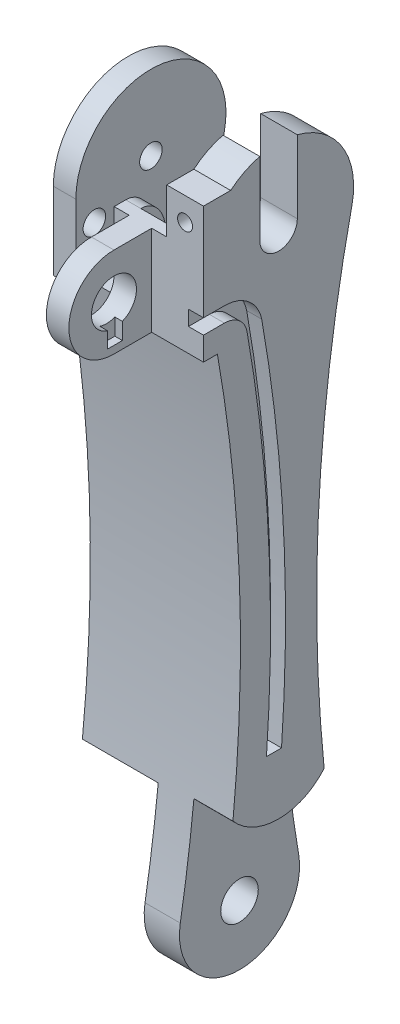
SolidWorks part; units mm, degrees
ref_plane "Front Plane" through (0, 0, 0) normal (0, 0, 1) x (1, 0, 0)
ref_plane "Top Plane" through (0, 0, 0) normal (0, 1, 0) x (1, 0, 0)
ref_plane "Right Plane" through (0, 0, 0) normal (1, 0, 0) x (0, 0, -1)
sketch "Sketch1" plane through (0, 0, 0) normal (1, 0, 0) x (0, 0, -1)
  arc A0 (9.7654, 20.1165) -> (-9.7654, 20.1165) centre (0, 22.2701) ccw
  arc A1 (-7.8874, -56.3924) -> (7.8874, -56.3924) centre (0, -57.7299) ccw
  arc A2 (-7.8874, -56.3924) -> (-9.7654, 20.1165) centre (-205.0724, -22.9549) ccw
  circle A3 centre (0, 22.2701) radius 1.5
  arc A4 (9.7654, 20.1165) -> (7.8874, -56.3924) centre (205.0724, -22.9549) ccw
  circle A5 centre (0, -57.7299) radius 2.5
extrude "Boss-Extrude1" add sketch "Sketch1" along normal blind 20
sketch "Sketch2" plane through (0, 0, 0) normal (0, 0, 1) x (1, 0, 0)
  line L1 (0, -65.7299) -> (8.1, -65.7299)
  line L2 (0, -65.7299) -> (0, -45.7299)
  line L3 (0, -45.7299) -> (8.1, -45.7299)
  line L4 (8.1, -65.7299) -> (8.1, -45.7299)
  line L5 (20, -65.7299) -> (14.8, -65.7299)
  line L6 (20, -65.7299) -> (20, -45.7299)
  line L7 (20, -45.7299) -> (14.8, -45.7299)
  line L8 (14.8, -65.7299) -> (14.8, -45.7299)
  line L11 (3, 32.2701) -> (8.1, 32.2701)
  line L12 (3, 32.2701) -> (3, 12.2701)
  line L13 (3, 12.2701) -> (8.1, 12.2701)
  line L14 (8.1, 32.2701) -> (8.1, 12.2701)
extrude "Cut-Extrude1" cut sketch "Sketch2" against normal blind 20 and the other way blind 20
sketch "Sketch3" plane through (8.1, 0, 0) normal (-1, 0, 0) x (0, 0, 1)
  line L0 (8.5, 22.2701) -> (8.5, 40.9095)
  line L1 (8.5, 40.9095) -> (-17.5287, 40.9095)
  line L2 (-17.5287, 40.9095) -> (-17.5287, 13.7701)
  line L3 (0, 13.7701) -> (-17.5287, 13.7701)
  arc A0 (0, 13.7701) -> (8.5, 22.2701) centre (0, 22.2701) ccw
extrude "Cut-Extrude2" cut sketch "Sketch3" against normal blind 9
sketch "Sketch4" plane through (8.1, 0, 0) normal (-1, 0, 0) x (0, 0, 1)
  line L0 (8.5, 27.5379) -> (8.2838, 12.7416)
  line L1 (8.2838, 12.7416) -> (10.2838, 12.7416)
  line L2 (10.2838, 12.7416) -> (10.2838, 27.5379)
  line L3 (10.2838, 27.5379) -> (8.5, 27.5379)
  arc A0 (9.7654, 20.1165) -> (6.3734, -45.7299) centre (205.0724, -22.9549) ccw construction
extrude "Boss-Extrude2" add sketch "Sketch4" against normal through all
sketch "Sketch5" plane through (8.1, 0, 0) normal (-1, 0, 0) x (0, 0, 1)
  line L4 (8.1452, 11.9686) -> (8.4478, 23.9686)
  line L6 (15.0224, 23.9686) -> (9.8547, 23.9686)
  line L8 (8.1452, 11.9686) -> (15.0224, 11.9686)
  line L9 (8.5, 27.5379) -> (8.4045, 20.9993) construction
  line L10 (8.4478, 23.9686) -> (9.8547, 23.9686)
  circle A2 centre (15.0224, 17.9686) radius 3
  arc A5 (15.0224, 11.9686) -> (15.0224, 23.9686) centre (15.0224, 17.9686) ccw
  arc A6 (9.7654, 20.1165) -> (-9.7654, 20.1165) centre (0, 22.2701) ccw construction
  arc A7 (9.7654, 20.1165) -> (6.3734, -45.7299) centre (205.0724, -22.9549) ccw construction
extrude "Boss-Extrude3" add sketch "Sketch5" against normal blind 5
sketch "Sketch12" plane through (13.1, 0, 0) normal (1, 0, 0) x (0, 0, -1)
  line L2 (-13.9029, 14.9686) -> (-13.9029, 12.9686)
  line L4 (-15.9029, 14.9686) -> (-15.9029, 15.2943)
  line L5 (-15.9029, 15.2943) -> (-13.9029, 15.2943)
  line L6 (-13.9029, 12.9686) -> (-15.9029, 12.9686)
  line L7 (-13.9029, 14.9686) -> (-13.9029, 15.2943)
  line L11 (-15.9029, 14.9686) -> (-15.9029, 12.9686)
extrude "Cut-Extrude6" cut sketch "Sketch12" against normal blind 1
sketch "Sketch13" plane through (17.1, 0, 0) normal (-1, 0, 0) x (0, 0, 1)
  circle A0 centre (0, 22.2701) radius 2.5
extrude "Cut-Extrude7" cut sketch "Sketch13" against normal blind 4
sketch "Sketch15" plane through (0, 0, 0) normal (-1, 0, 0) x (0, 0, 1)
  line L0 (10, 22.2701) -> (10, 11.9686)
  line L1 (8.1452, 11.9686) -> (15.0224, 11.9686) construction
  line L2 (10, 11.9686) -> (8.1452, 11.9686)
  line L3 (10, 22.2701) -> (7.5957, 11.9686)
  line L4 (7.5957, 11.9686) -> (8.1452, 11.9686)
  arc A0 (9.7654, 20.1165) -> (-9.7654, 20.1165) centre (0, 22.2701) ccw construction
extrude "Boss-Extrude4" add sketch "Sketch15" against normal blind 3
sketch "Sketch16" plane through (20, 0, 0) normal (1, 0, 0) x (0, 0, -1)
  line L0 (-10.2838, 23.9686) -> (-9.8547, 23.9686)
  line L1 (-10.2838, 23.9686) -> (-10.2838, 27.5379)
  line L2 (-10.2838, 27.5379) -> (-8.5, 27.5379) construction
  line L3 (-10.2838, 12.7416) -> (-10.2838, 27.5379) construction
  line L4 (-10.2838, 27.5379) -> (-8.5, 27.5379)
  arc A0 (-8.5, 27.5379) -> (-9.8547, 23.9686) centre (0, 22.2701) ccw
extrude "Cut-Extrude9" cut sketch "Sketch16" against normal blind 3
sketch "Sketch17" plane through (0, 0, 10.2838) normal (0, 0, 1) x (1, 0, 0)
  line L1 (17.1, 27.5379) -> (8.1, 27.5379)
  line L2 (17.1, 27.5379) -> (17.1, 23.9686)
  line L3 (17.1, 23.9686) -> (8.1, 23.9686)
  line L4 (8.1, 27.5379) -> (8.1, 23.9686)
extrude "Cut-Extrude11" cut sketch "Sketch17" against normal blind 3
sketch "Sketch18" plane through (13.1, 0, 0) normal (1, 0, 0) x (0, 0, -1)
  line L1 (-10.2838, 12.7416) -> (-4.5128, 12.7416)
  line L2 (-10.2838, 12.7416) -> (-10.2838, 11.9686)
  line L3 (-10.2838, 11.9686) -> (-4.5128, 11.9686)
  line L4 (-4.5128, 12.7416) -> (-4.5128, 11.9686)
extrude "Boss-Extrude5" add sketch "Sketch18" along normal through all and the other way blind 1
sketch "Sketch19" plane through (0, 12.2701, 0) normal (0, 1, 0) x (1, 0, 0)
  line L1 (8.1, -8.1989) -> (3, -8.1989)
  line L2 (8.1, -8.1989) -> (8.1, 8.1989)
  line L3 (8.1, 8.1989) -> (3, 8.1989)
  line L4 (3, -8.1989) -> (3, 8.1989)
extrude "Cut-Extrude12" cut sketch "Sketch19" against normal up to surface (0.3015 mm away) up to face at (1.5, 11.9686, 9.0726)
sketch "Sketch20" plane through (17.1, 0, 0) normal (-1, 0, 0) x (0, 0, 1)
  line L1 (2.5, 22.2701) -> (-2.5, 22.2701)
  line L2 (2.5, 22.2701) -> (2.5, 34.6894)
  line L3 (2.5, 34.6894) -> (-2.5, 34.6894)
  line L4 (-2.5, 22.2701) -> (-2.5, 34.6894)
  circle A0 centre (0, 22.2701) radius 2.5 construction
extrude "Cut-Extrude13" cut sketch "Sketch20" against normal blind 10
sketch "Sketch21" plane through (17.1, 0, 0) normal (-1, 0, 0) x (0, 0, 1)
  line L1 (-8.4732, 13.7701) -> (0.2785, 12.274)
  line L3 (2.5, 22.2701) -> (2.5, 31.9526)
  line L5 (-2.5, 22.2701) -> (-2.5, 31.9526)
  arc A0 (0.2785, 12.274) -> (2.5, 31.9526) centre (0, 22.2701) ccw
  arc A1 (-2.5, 22.2701) -> (2.5, 22.2701) centre (0, 22.2701) ccw
  arc A2 (-2.5, 31.9526) -> (-9.7654, 20.1165) centre (0, 22.2701) ccw
  arc A7 (-8.4732, 13.7701) -> (-9.7654, 20.1165) centre (-205.0724, -22.9549) ccw
extrude "Boss-Extrude6" add sketch "Sketch21" along normal blind 2
sketch "Sketch23" plane through (0, 0, 10.2838) normal (0, 0, 1) x (1, 0, 0)
  line L1 (15.1, 23.9686) -> (20, 23.9686)
  line L2 (15.1, 23.9686) -> (15.1, 29.9686)
  line L3 (15.1, 29.9686) -> (20, 29.9686)
  line L4 (20, 23.9686) -> (20, 29.9686)
extrude "Boss-Extrude7" add sketch "Sketch23" against normal blind 4
sketch "Sketch22" plane through (0, 0, 10.2838) normal (0, 0, 1) x (1, 0, 0)
  circle A1 centre (17.55, 26.8701) radius 1
extrude "Cut-Extrude15" cut sketch "Sketch22" against normal blind 8
sketch "Sketch24" plane through (8.1, 0, 0) normal (-1, 0, 0) x (0, 0, 1)
  line L0 (5.1478, 19.7374) -> (5.1478, 15.5063)
  line L2 (8.4478, 23.9686) -> (8.4478, 15.5063)
  line L3 (8.4478, 15.5063) -> (5.1478, 15.5063)
  arc A0 (0, 13.7701) -> (8.3673, 20.7738) centre (0, 22.2701) ccw construction
  ellipse E0 centre (8.4478, 19.7374) end of major axis (8.4478, 15.5063) minor radius 3.3 (8.4478, 23.9686) -> (5.1478, 19.7374) ccw
extrude "Boss-Extrude8" add sketch "Sketch24" against normal blind 2
sketch "Sketch14" plane through (0, 0, 0) normal (-1, 0, 0) x (0, 0, 1)
  circle A3 centre (7.5326, 18.3318) radius 1.5
extrude "Cut-Extrude8" cut sketch "Sketch14" against normal up to surface (10.1 mm away) up to face at (10.1, 20.14, 6.7306)
sketch "Sketch25" plane through (8.1, 0, 0) normal (-1, 0, 0) x (0, 0, 1)
  line L0 (12, -45.7299) -> (8.3462, -36.9607)
  line L1 (-12, -45.7299) -> (-12, -57.7299)
  line L2 (12, -45.7299) -> (12, -57.7299)
  line L3 (-12, -45.7299) -> (-8.3462, -36.9607)
  line L5 (2.5, -53.2274) -> (2.5, -45.7299)
  line L7 (-2.5, -53.2274) -> (-2.5, -45.7299)
  arc A0 (-2.5, -53.2274) -> (2.5, -53.2274) centre (0, -57.7299) ccw
  arc A1 (-12, -57.7299) -> (12, -57.7299) centre (0, -57.7299) ccw
  arc A2 (2.5, -45.7299) -> (8.3462, -36.9607) centre (0, -37.7299) ccw
  arc A4 (-8.3462, -36.9607) -> (-2.5, -45.7299) centre (0, -37.7299) ccw
extrude "Cut-Extrude17" cut sketch "Sketch25" against normal blind 2 and the other way up to surface (8.1 mm away) other way up to face at (0, 18.3318, 9.0326)
sketch "Sketch26" plane through (20, 0, 0) normal (1, 0, 0) x (0, 0, -1)
  line L0 (-10.2838, 11.9686) -> (-10.2838, 29.9686) construction
  line L1 (-7.21, 15.0854) -> (-10.2838, 15.0854)
  line L3 (-7.21, 17.0854) -> (-10.2838, 17.0854)
  line L4 (-10.2838, 15.0854) -> (-10.2838, 17.0854)
  line L8 (-1.6082, -37.73) -> (0.397, -37.73)
  arc A0 (-4.2066, 12.6671) -> (-7.21, 15.0854) centre (-7.21, 12.0113) ccw
  arc A1 (-2.2434, 13.0504) -> (-7.21, 17.0854) centre (-7.21, 12.0113) ccw
  arc A2 (-2.3994, -46.1854) -> (-4.2066, 12.6671) centre (-205.0724, -22.9549) ccw
  arc A3 (-1.6082, -37.73) -> (-4.2066, 12.6671) centre (-205.0724, -22.9549) ccw
  circle A4 centre (-7.21, 12.0113) radius 5.0741 construction
  circle A5 centre (-7.21, 12.0113) radius 3.0741 construction
  arc A6 (-0.4124, -46.4131) -> (-2.2373, 13.0163) centre (-205.0724, -22.9549) ccw
  arc A7 (0.397, -37.73) -> (-2.2434, 13.0504) centre (-205.0724, -22.9549) ccw
  dimension "D3" = 2
  dimension "D1" = 4
  dimension "D2" = 6
extrude "Cut-Extrude18" cut sketch "Sketch26" against normal blind 2
sketch "Sketch29" plane through (20, 0, 0) normal (1, 0, 0) x (0, 0, -1)
  line L1 (8, -37.7299) -> (8.1403, -37.7299)
  line L2 (-15.7549, -37.7299) -> (-8, -37.7299)
  line L3 (-15.7549, -37.7299) -> (-15.7549, -45.9375)
  line L4 (-15.7549, -45.9375) -> (8.1403, -45.9375)
  line L5 (8.1403, -37.7299) -> (8.1403, -45.9375)
  arc A0 (-8, -37.7299) -> (8, -37.7299) centre (0, -37.7299) ccw
extrude "Cut-Extrude20" cut sketch "Sketch29" against normal up to surface (5.2 mm away) up to face at (14.8, -57.7299, -2.5)
sketch "Sketch30" plane through (0, 0, 10.2838) normal (0, 0, 1) x (1, 0, 0)
  line L1 (13.1, 11.9686) -> (20, 11.9686)
  line L2 (13.1, 11.9686) -> (13.1, 31.9686)
  line L3 (13.1, 31.9686) -> (20, 31.9686)
  line L4 (20, 11.9686) -> (20, 31.9686)
extrude "Cut-Extrude21" cut sketch "Sketch30" against normal up to surface (0.2838 mm away) up to face at (1.5, 17.1194, 10)
sketch "Sketch31" plane through (0, 23.9686, 0) normal (0, 1, 0) x (1, 0, 0)
  line L0 (8.1, -15.0224) -> (8.1, -8.4478) construction
  line L1 (8.1, -10) -> (10.1, -10)
  line L2 (8.1, -10) -> (8.1, -21.0224)
  line L3 (8.1, -21.0224) -> (10.1, -21.0224)
  line L4 (10.1, -10) -> (10.1, -21.0224)
  line L5 (8.1, -21.0224) -> (13.1, -21.0224) construction
extrude "Cut-Extrude22" cut sketch "Sketch31" against normal up to next
sketch "Sketch32" plane through (8.1, 0, 0) normal (-1, 0, 0) x (0, 0, 1)
  line L0 (-8.4732, 13.7701) -> (-8.4732, 5.4011)
  line L2 (5.1478, 15.5063) -> (-8.4732, 5.4011)
  line L5 (5.1478, 15.5063) -> (-8.4732, 13.7701)
extrude "Cut-Extrude23" cut sketch "Sketch32" against normal blind 7
